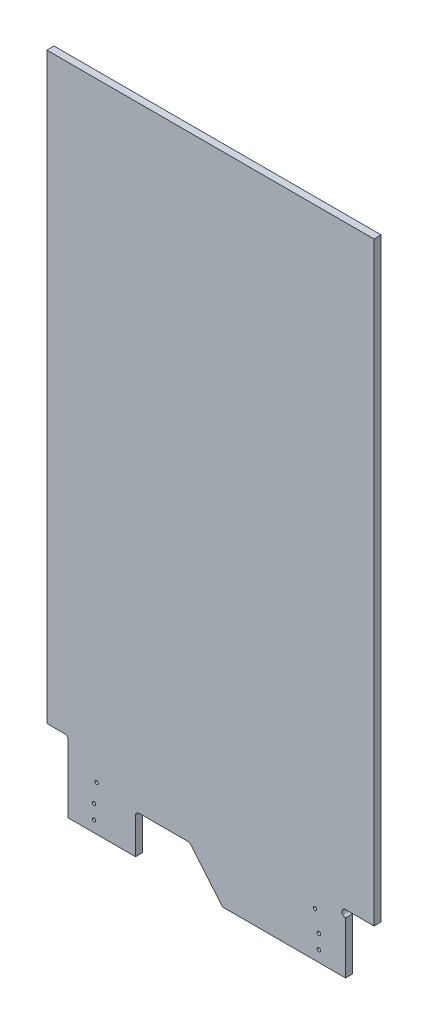
SolidWorks part; units mm, degrees
material "Maple"
ref_plane "Front Plane" through (0, 0, 0) normal (0, 0, 1) x (1, 0, 0)
ref_plane "Top Plane" through (0, 0, 0) normal (0, 1, 0) x (1, 0, 0)
ref_plane "Right Plane" through (0, 0, 0) normal (1, 0, 0) x (0, 0, -1)
sketch "Sketch1" plane through (0, 0, 0) normal (0, 0, 1) x (1, 0, 0)
  line L0 (313.7488, 0) -> (533.4, 0)
  line L1 (38.1, 0) -> (158.3263, 0)
  line L2 (584.2, 105.7904) -> (584.2, 1168.4)
  line L3 (0, 1168.4) -> (0, 127)
  line L4 (0, 1168.4) -> (584.2, 1168.4)
  line L5 (38.1, 0) -> (38.1, 120.65)
  line L6 (31.75, 127) -> (0, 127)
  line L7 (256.7734, 68.1669) -> (313.7488, 0)
  line L8 (164.6763, 70.4446) -> (251.9012, 70.4446)
  line L9 (158.3263, 0) -> (158.3263, 64.0946)
  line L10 (533.4, 93.0904) -> (533.4, 0)
  line L11 (533.4, 105.7904) -> (584.2, 105.7904)
  circle A0 centre (84.1361, 45.212) radius 3.1115
  circle A1 centre (84.1361, 19.812) radius 3.1115
  circle A2 centre (88.8986, 80.137) radius 3.1115
  arc A3 (38.1, 120.65) -> (31.75, 127) centre (31.75, 120.65) ccw
  arc A4 (256.7734, 68.1669) -> (251.9012, 70.4446) centre (251.9012, 64.0946) ccw
  arc A5 (164.6763, 70.4446) -> (158.3263, 64.0946) centre (164.6763, 64.0946) ccw
  arc A6 (533.4, 105.7904) -> (533.4, 93.0904) centre (533.4, 99.4404) ccw
  circle A7 centre (485.7736, 19.812) radius 3.1115
  circle A8 centre (478.7886, 80.137) radius 3.1115
  circle A9 centre (485.7736, 45.212) radius 3.1115
sketch "Sketch2" plane through (0, 0, 0) normal (0, 0, 1) x (1, 0, 0)
  line L0 (0, 1168.4) -> (0, 0)
  line L1 (0, 0) -> (584.2, 0)
  line L2 (584.2, 0) -> (584.2, 1168.4)
  line L3 (584.2, 1168.4) -> (0, 1168.4)
  line L4 (292.1, 1168.4) -> (292.1, 0) construction
  line L5 (292.1, 584.2) -> (0, 584.2) construction
  line L6 (292.1, 584.2) -> (584.2, 584.2) construction
  dimension "D1" = 584.2
  dimension "D2" = 1168.4
extrude "Extrude1" add sketch "Sketch2" against normal blind 12.7
sketch "Sketch3" plane through (0, 0, 0) normal (0, 0, 1) x (1, 0, 0)
  circle A0 centre (84.1361, 19.812) radius 3.1115
  circle A1 centre (84.1361, 45.212) radius 3.1115
  circle A2 centre (88.8986, 80.137) radius 3.1115
  circle A3 centre (485.7736, 19.812) radius 3.1115
  circle A4 centre (485.7736, 45.212) radius 3.1115
  circle A5 centre (478.7886, 80.137) radius 3.1115
extrude "Cut-Extrude1" cut sketch "Sketch3" against normal up to surface (12.7 mm away) up to face at (292.1, 584.2, -12.7)
sketch "Sketch4" plane through (0, 0, 0) normal (0, 0, 1) x (1, 0, 0)
  line L0 (0, 127) -> (31.75, 127)
  line L1 (38.1, 120.65) -> (38.1, 0)
  line L2 (38.1, 0) -> (0, 0)
  line L3 (0, 0) -> (0, 127)
  line L4 (0, 0) -> (584.2, 0) construction
  line L5 (0, 1168.4) -> (0, 0) construction
  arc A0 (31.75, 127) -> (38.1, 120.65) centre (31.75, 120.65) cw
  dimension "D3" = 6.35
  dimension "D1" = 127
  dimension "D2" = 38.1
extrude "Cut-Extrude2" cut sketch "Sketch4" against normal up to surface (12.7 mm away) up to face at (475.6771, 80.137, -12.7)
sketch "Sketch5" plane through (0, 0, 0) normal (0, 0, 1) x (1, 0, 0)
  line L0 (584.2, 105.791) -> (533.4, 105.791)
  line L1 (533.4, 93.091) -> (533.4, 0)
  line L2 (533.4, 0) -> (584.2, 0)
  line L3 (584.2, 0) -> (584.2, 105.791)
  line L4 (38.1, 0) -> (584.2, 0) construction
  line L5 (584.2, 0) -> (584.2, 1168.4) construction
  arc A0 (533.4, 105.791) -> (533.4, 93.091) centre (533.4, 99.441) ccw
  dimension "D3" = 6.35
  dimension "D1" = 50.8
  dimension "D2" = 105.791
  dimension "D4" = 12.7
extrude "Cut-Extrude3" cut sketch "Sketch5" against normal up to surface (12.7 mm away) up to face at (182.5236, 387.5379, -12.7)
sketch "Sketch7" plane through (0, 0, 0) normal (0, 0, 1) x (1, 0, 0)
  line L0 (158.3263, 0) -> (158.3263, 64.0946)
  line L1 (164.6763, 70.4446) -> (251.9012, 70.4446)
  line L2 (256.7734, 68.1669) -> (313.7488, 0)
  line L3 (313.7488, 0) -> (158.3263, 0)
  arc A0 (158.3263, 64.0946) -> (164.6763, 70.4446) centre (164.6763, 64.0946) cw
  arc A1 (251.9012, 70.4446) -> (256.7734, 68.1669) centre (251.9012, 64.0946) cw
extrude "Cut-Extrude4" cut sketch "Sketch7" against normal up to surface (12.7 mm away) up to face at (287.1515, 301.7438, -12.7)
